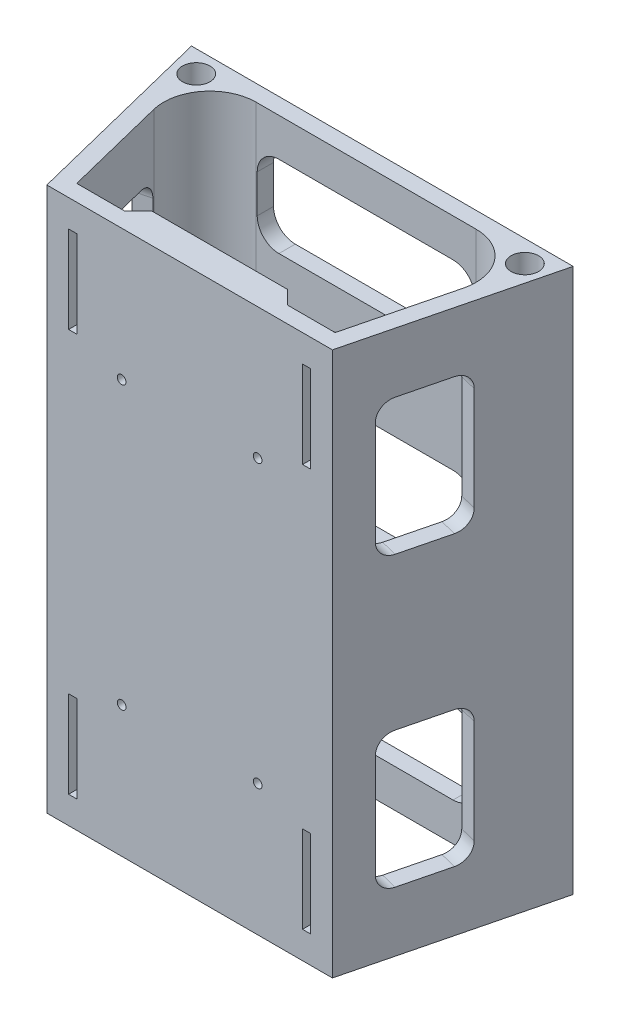
SolidWorks part; units mm, degrees
ref_plane "Front Plane" through (0, 0, 0) normal (0, 0, 1) x (1, 0, 0)
ref_plane "Top Plane" through (0, 0, 0) normal (0, 1, 0) x (1, 0, 0)
ref_plane "Right Plane" through (0, 0, 0) normal (1, 0, 0) x (0, 0, -1)
sketch "Sketch1" plane through (0, 0, 0) normal (0, 1, 0) x (1, 0, 0)
  line L0 (-45.2807, -29.0359) -> (49.7193, -29.0359)
  line L7 (-59.9509, 29.803) -> (64.3895, 29.803)
  line L8 (-59.9509, 29.803) -> (-45.2807, -29.0359)
  line L9 (49.7193, -29.0359) -> (64.3895, 29.803)
  line L10 (-67.9428, 35.803) -> (72.3814, 35.803)
  line L11 (-50.2807, -35.0359) -> (54.7193, -35.0359)
  line L12 (-67.9428, 35.803) -> (-50.2807, -35.0359)
  line L13 (54.7193, -35.0359) -> (72.3814, 35.803)
  point P0 (0, 0)
  point P6 (0, 0)
  point P9 (2.2193, -29.0359)
  point P11 (2.2193, 29.803)
  point P13 (2.2193, 35.803)
  point P16 (2.2193, -35.0359)
  dimension "D3" = 95
  dimension "D4" = 6
  dimension "D5" = 104
  dimension "D6" = 0
  dimension "D7" = 105
  dimension "D8" = 0
  dimension "D9" = 6
  dimension "D10" = 104
  dimension "D11" = 104
  dimension "D12" = 104
extrude "Boss-Extrude2" add sketch "Sketch1" along normal blind 200
fillet "Fillet2" radius 17 2 edges at (64.3895, 100, -29.803) (-59.9509, 100, -29.803)
sketch "Sketch3" plane through (0, 200, 0) normal (0, 1, 0) x (1, 0, 0)
  line L0 (72.3814, 35.803) -> (-67.9428, 35.803) construction
  circle A0 centre (-58.1928, 27.803) radius 5.05
  circle A1 centre (62.6314, 27.803) radius 5.05
  dimension "D1" = 9.75
  dimension "D3" = 9.75
  dimension "D2" = 8
  dimension "D4" = 8
extrude "Cut-Extrude1" cut sketch "Sketch3" against normal blind 200
sketch "Sketch4" plane through (0, 0, -35.803) normal (0, 0, -1) x (-1, 0, 0)
  line L0 (-72.3814, 200) -> (67.9428, 200) construction
  line L2 (67.9428, 200) -> (67.9428, 0) construction
  circle A1 centre (9.0928, 60) radius 1.3
  circle A2 centre (-13.5272, 60) radius 1.3
  circle A3 centre (9.0928, 140) radius 1.3
  circle A4 centre (-2.2172, 140) radius 1.3
  circle A5 centre (-13.5272, 140) radius 1.3
  circle A6 centre (-2.2172, 60) radius 1.3
  dimension "D1" = 22.62
  dimension "D4" = 22.62
  dimension "D2" = 11.31
  dimension "D3" = 70.16
  dimension "D5" = 11.31
  dimension "D6" = 70.16
  dimension "D7" = 80
  dimension "D8" = 60
  dimension "D10" = 60
extrude "Cut-Extrude3" cut sketch "Sketch4" against normal blind 35
sketch "Sketch5" plane through (0, 0, -35.803) normal (0, 0, -1) x (-1, 0, 0)
  line L1 (-42.2172, 81) -> (37.7828, 81)
  line L2 (-42.2172, 81) -> (-42.2172, 119)
  line L3 (-42.2172, 119) -> (37.7828, 119)
  line L4 (37.7828, 81) -> (37.7828, 119)
  line L5 (-42.2172, 81) -> (37.7828, 119) construction
  line L6 (-42.2172, 119) -> (37.7828, 81) construction
  line L9 (-72.3814, 200) -> (67.9428, 200) construction
  line L10 (-42.2172, 156) -> (37.7828, 156)
  line L11 (-42.2172, 156) -> (-42.2172, 186)
  line L12 (-42.2172, 186) -> (37.7828, 186)
  line L13 (37.7828, 156) -> (37.7828, 186)
  line L14 (-42.2172, 156) -> (37.7828, 186) construction
  line L15 (-42.2172, 186) -> (37.7828, 156) construction
  line L17 (-72.3814, 0) -> (67.9428, 0) construction
  line L18 (-42.2172, 14) -> (37.7828, 14)
  line L19 (-42.2172, 14) -> (-42.2172, 44)
  line L20 (-42.2172, 44) -> (37.7828, 44)
  line L21 (37.7828, 14) -> (37.7828, 44)
  line L22 (-42.2172, 14) -> (37.7828, 44) construction
  line L23 (-42.2172, 44) -> (37.7828, 14) construction
  circle A0 centre (-2.2172, 140) radius 1.3 construction
  circle A1 centre (-2.2172, 60) radius 1.3 construction
  point P0 (-2.2172, 100)
  point P9 (-2.2172, 171)
  point P16 (-2.2172, 29)
  dimension "D1" = 0
  dimension "D2" = 38
  dimension "D3" = 80
  dimension "D4" = 80
  dimension "D5" = 30
  dimension "D6" = 14
  dimension "D7" = 30
  dimension "D8" = 80
  dimension "D9" = 14
  dimension "D10" = 0
  dimension "D11" = 0
extrude "Cut-Extrude4" cut sketch "Sketch5" against normal blind 21
fillet "Fillet3" radius 8 12 edges at (-37.7828, 119, -32.803) (-37.7828, 44, -32.803) (-37.7828, 186, -32.803) (-37.7828, 156, -32.803) (-37.7828, 81, -32.803) (-37.7828, 14, -32.803) (42.2172, 14, -32.803) (42.2172, 156, -32.803) (42.2172, 81, -32.803) (42.2172, 186, -32.803) (42.2172, 119, -32.803) (42.2172, 44, -32.803)
sketch "Sketch6" plane through (0, 0, 35.0359) normal (0, 0, 1) x (1, 0, 0)
  line L0 (-50.2807, 200) -> (-50.2807, 0) construction
  line L1 (-42.2807, 190) -> (-39.2807, 190)
  line L2 (-42.2807, 190) -> (-42.2807, 158)
  line L3 (-42.2807, 158) -> (-39.2807, 158)
  line L4 (-39.2807, 190) -> (-39.2807, 158)
  line L5 (-42.2807, 10) -> (-39.2807, 10)
  line L6 (-42.2807, 10) -> (-42.2807, 42)
  line L7 (-42.2807, 42) -> (-39.2807, 42)
  line L8 (-39.2807, 10) -> (-39.2807, 42)
  line L9 (46.7193, 10) -> (43.7193, 10)
  line L10 (46.7193, 10) -> (46.7193, 42)
  line L11 (46.7193, 42) -> (43.7193, 42)
  line L12 (43.7193, 10) -> (43.7193, 42)
  line L13 (46.7193, 158) -> (43.7193, 158)
  line L14 (46.7193, 158) -> (46.7193, 190)
  line L15 (46.7193, 190) -> (43.7193, 190)
  line L16 (43.7193, 158) -> (43.7193, 190)
  line L17 (54.7193, 200) -> (54.7193, 0) construction
  line L18 (-50.2807, 200) -> (54.7193, 200) construction
  line L19 (-50.2807, 0) -> (54.7193, 0) construction
  dimension "D1" = 32
  dimension "D2" = 32
  dimension "D3" = 32
  dimension "D4" = 32
  dimension "D5" = 3
  dimension "D6" = 3
  dimension "D7" = 3
  dimension "D8" = 3
  dimension "D9" = 8
  dimension "D10" = 8
  dimension "D11" = 8
  dimension "D12" = 8
  dimension "D13" = 10
  dimension "D14" = 10
  dimension "D15" = 10
  dimension "D16" = 10
extrude "Cut-Extrude5" cut sketch "Sketch6" against normal blind 21
sketch "Sketch8" plane through (59.741, 0, 14.8951) normal (0.9703, 0, 0.2419) x (0.2419, 0, -0.9703)
  line L0 (52.2501, 200) -> (52.2501, 0) construction
  line L1 (-7.7499, 72) -> (22.2501, 72)
  line L2 (-7.7499, 72) -> (-7.7499, 22)
  line L3 (-7.7499, 22) -> (22.2501, 22)
  line L4 (22.2501, 72) -> (22.2501, 22)
  line L5 (-7.7499, 72) -> (22.2501, 22) construction
  line L6 (-7.7499, 22) -> (22.2501, 72) construction
  line L7 (-20.7574, 0) -> (52.2501, 0) construction
  line L8 (-20.7574, 200) -> (52.2501, 200) construction
  line L9 (22.2501, 128) -> (-7.7499, 128)
  line L10 (22.2501, 128) -> (22.2501, 178)
  line L11 (22.2501, 178) -> (-7.7499, 178)
  line L12 (-7.7499, 128) -> (-7.7499, 178)
  point P0 (7.2501, 47)
  dimension "D1" = 30
  dimension "D2" = 50
  dimension "D3" = 30
  dimension "D4" = 22
  dimension "D5" = 50
  dimension "D6" = 22
  dimension "D7" = 30
  dimension "D8" = 30
extrude "Cut-Extrude6" cut sketch "Sketch8" against normal blind 21
fillet "Fillet4" radius 6 8 edges at (54.8082, 22, 21.6524) (54.8082, 128, 21.6524) (54.8082, 72, 21.6524) (54.8082, 178, 21.6524) (62.0659, 178, -7.4565) (62.0659, 72, -7.4565) (62.0659, 22, -7.4565) (62.0659, 128, -7.4565)
sketch "Sketch9" plane through (-55.5621, 0, 13.8532) normal (-0.9703, 0, 0.2419) x (0.2419, 0, 0.9703)
  line L0 (-51.1763, 0) -> (21.8312, 0) construction
  line L1 (8.8237, 22) -> (-21.1763, 22)
  line L2 (8.8237, 22) -> (8.8237, 72)
  line L3 (8.8237, 72) -> (-21.1763, 72)
  line L4 (-21.1763, 22) -> (-21.1763, 72)
  line L5 (-51.1763, 200) -> (-51.1763, 0) construction
  line L6 (-51.1763, 200) -> (21.8312, 200) construction
  line L7 (-21.1763, 128) -> (8.8237, 128)
  line L8 (-21.1763, 128) -> (-21.1763, 178)
  line L9 (-21.1763, 178) -> (8.8237, 178)
  line L10 (8.8237, 128) -> (8.8237, 178)
  dimension "D1" = 22
  dimension "D2" = 30
  dimension "D3" = 30
  dimension "D4" = 50
  dimension "D5" = 22
  dimension "D6" = 30
  dimension "D7" = 30
  dimension "D8" = 50
extrude "Cut-Extrude7" cut sketch "Sketch9" against normal blind 21
fillet "Fillet5" radius 6 8 edges at (-50.3696, 22, 21.6524) (-57.6273, 22, -7.4565) (-57.6273, 128, -7.4565) (-50.3696, 128, 21.6524) (-50.3696, 72, 21.6524) (-57.6273, 72, -7.4565) (-57.6273, 178, -7.4565) (-50.3696, 178, 21.6524)
sketch "Sketch10" plane through (0, 0, 29.0359) normal (0, 0, -1) x (-1, 0, 0)
  line L0 (45.2807, 0) -> (-49.7193, 0) construction
  line L1 (-32.2193, 0) -> (27.7807, 0)
  line L2 (-32.2193, 0) -> (-32.2193, 2.25)
  line L3 (-32.2193, 2.25) -> (27.7807, 2.25)
  line L4 (27.7807, 0) -> (27.7807, 2.25)
  line L5 (45.2807, 200) -> (45.2807, 0) construction
  point P6 (27.7807, 1.125)
  dimension "D1" = 60
  dimension "D2" = 2.25
  dimension "D3" = 17.5
extrude "Boss-Extrude3" add sketch "Sketch10" along normal blind 5
chamfer "Chamfer1" distance 5 angle 45 1 edges at (32.2193, 1.125, 24.0359)
chamfer "Chamfer2" distance 5 angle 45 1 edges at (-27.7807, 1.125, 24.0359)
fillet "Fillet6" radius 1 1 edges at (2.2193, 2.25, 29.0359)
sketch "Sketch11" plane through (0, 0, 29.0359) normal (0, 0, -1) x (-1, 0, 0)
  line L0 (45.2807, 200) -> (-49.7193, 200) construction
  line L1 (27.7807, 200) -> (-32.2193, 200)
  line L2 (27.7807, 200) -> (27.7807, 197.75)
  line L3 (27.7807, 197.75) -> (-32.2193, 197.75)
  line L4 (-32.2193, 200) -> (-32.2193, 197.75)
  line L5 (45.2807, 200) -> (45.2807, 0) construction
  dimension "D1" = 60
  dimension "D2" = 2.25
  dimension "D3" = 17.5
extrude "Boss-Extrude4" add sketch "Sketch11" along normal blind 5
chamfer "Chamfer3" distance 5 angle 45 2 edges at (32.2193, 198.875, 24.0359) (-27.7807, 198.875, 24.0359)
fillet "Fillet7" radius 1 1 edges at (2.2193, 197.75, 29.0359)
sketch "Sketch12" plane through (0, 0, 35.0359) normal (0, 0, 1) x (1, 0, 0)
  line L1 (-50.2807, 0) -> (54.7193, 0) construction
  line L2 (-50.2807, 200) -> (54.7193, 200) construction
  line L3 (54.7193, 200) -> (54.7193, 0) construction
  circle A0 centre (27.2193, 48.22) radius 1.6
  circle A1 centre (-22.7807, 48.22) radius 1.6
  circle A2 centre (27.2193, 151.78) radius 1.6
  circle A3 centre (-22.7807, 151.78) radius 1.6
  dimension "D1" = 50
  dimension "D2" = 50
  dimension "D3" = 103.56
  dimension "D4" = 48.22
  dimension "D5" = 27.5
  dimension "D6" = 27.5
  dimension "D7" = 48.22
extrude "Cut-Extrude9" cut sketch "Sketch12" against normal blind 21
sketch "Sketch13" plane through (0, 0, 29.0359) normal (0, 0, -1) x (-1, 0, 0)
  circle A0 centre (-27.2193, 48.22) radius 3
  circle A1 centre (22.7807, 48.22) radius 3
  circle A2 centre (-27.2193, 151.78) radius 3
  circle A3 centre (22.7807, 151.78) radius 3
extrude "Cut-Extrude10" cut sketch "Sketch13" against normal blind 2
